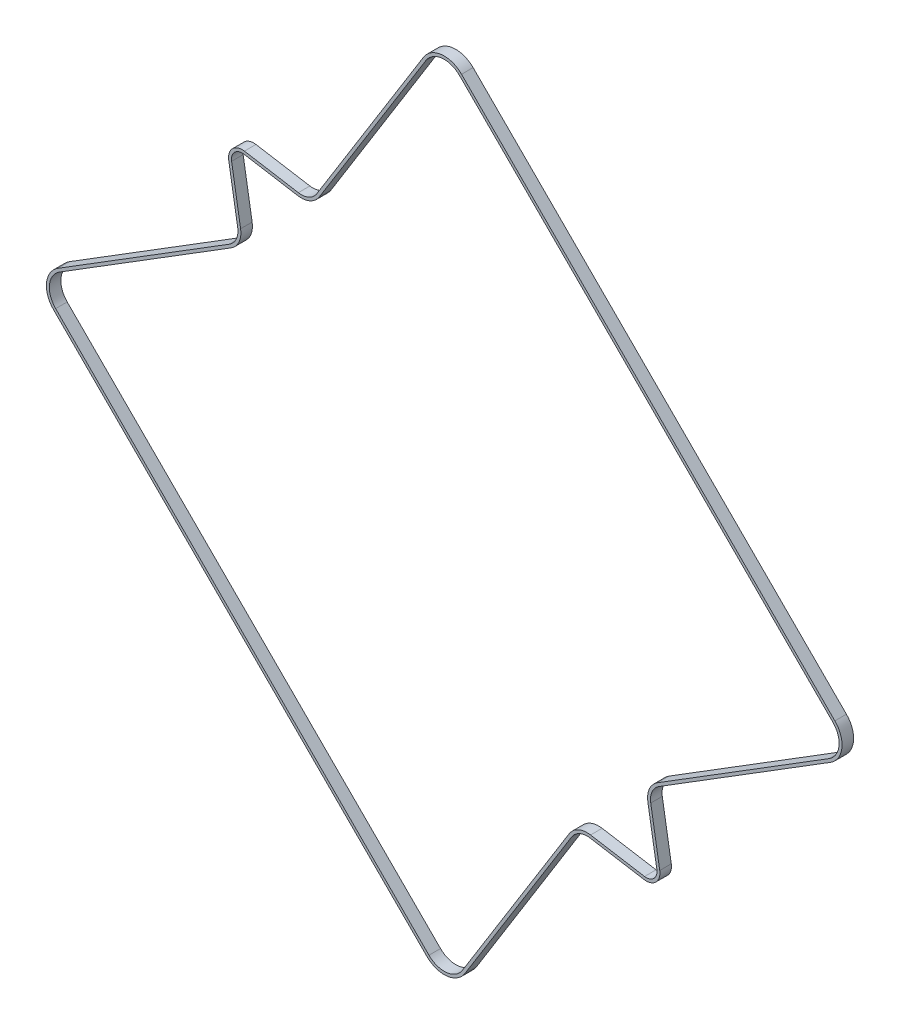
SolidWorks part; units mm, degrees
material "NEOPRENE"
ref_plane "Front Plane" through (0, 0, 0) normal (0, 0, 1) x (1, 0, 0)
ref_plane "Top Plane" through (0, 0, 0) normal (0, 1, 0) x (1, 0, 0)
ref_plane "Right Plane" through (0, 0, 0) normal (1, 0, 0) x (0, 0, -1)
sketch "Sketch2" plane through (0, 0, 0) normal (0, 0, 1) x (1, 0, 0)
  line L0 (0, 0) -> (1, 0) construction
  line L1 (0, 0) -> (0, 1) construction
  line L38 (-76.0535, -88.1779) -> (-104.0914, -83.5077)
  line L39 (-110.4923, -89.9086) -> (-105.8221, -117.9465)
  line L42 (76.0535, -299.8221) -> (104.0914, -304.4923)
  line L43 (110.4923, -298.0914) -> (105.8221, -270.0535)
  line L45 (-9.5229, 5.922) -> (-64.9051, -83.1363)
  line L46 (-110.8637, -129.0949) -> (-199.922, -184.4771)
  line L47 (9.5229, -393.922) -> (64.9051, -304.8637)
  line L48 (110.8637, -258.9051) -> (199.922, -203.5229)
  line L49 (-201.9296, -201.9296) -> (-7.9296, -395.9296)
  line L50 (201.9296, -186.0704) -> (7.9296, 7.9296)
  arc A1 (7.9296, 7.9296) -> (-9.5229, 5.922) centre (0, 0) ccw
  arc A4 (-199.922, -184.4771) -> (-201.9296, -201.9296) centre (-194, -194) ccw
  arc A10 (-7.9296, -395.9296) -> (9.5229, -393.922) centre (0, -388) ccw
  arc A13 (199.922, -203.5229) -> (201.9296, -186.0704) centre (194, -194) ccw
  arc A18 (-64.9051, -83.1363) -> (-76.0535, -88.1779) centre (-74.2462, -77.3274) cw
  arc A19 (-104.0914, -83.5077) -> (-110.4923, -89.9086) centre (-105.0054, -88.9946) ccw
  arc A20 (-105.8221, -117.9465) -> (-110.8637, -129.0949) centre (-116.6726, -119.7538) cw
  arc A21 (64.9051, -304.8637) -> (76.0535, -299.8221) centre (74.2462, -310.6726) cw
  arc A22 (104.0914, -304.4923) -> (110.4923, -298.0914) centre (105.0054, -299.0054) ccw
  arc A23 (105.8221, -270.0535) -> (110.8637, -258.9051) centre (116.6726, -268.2462) cw
extrude "Extrude-Thin1" add sketch "Sketch2" along normal blind 6 thin thin type one direction wall 1.52
